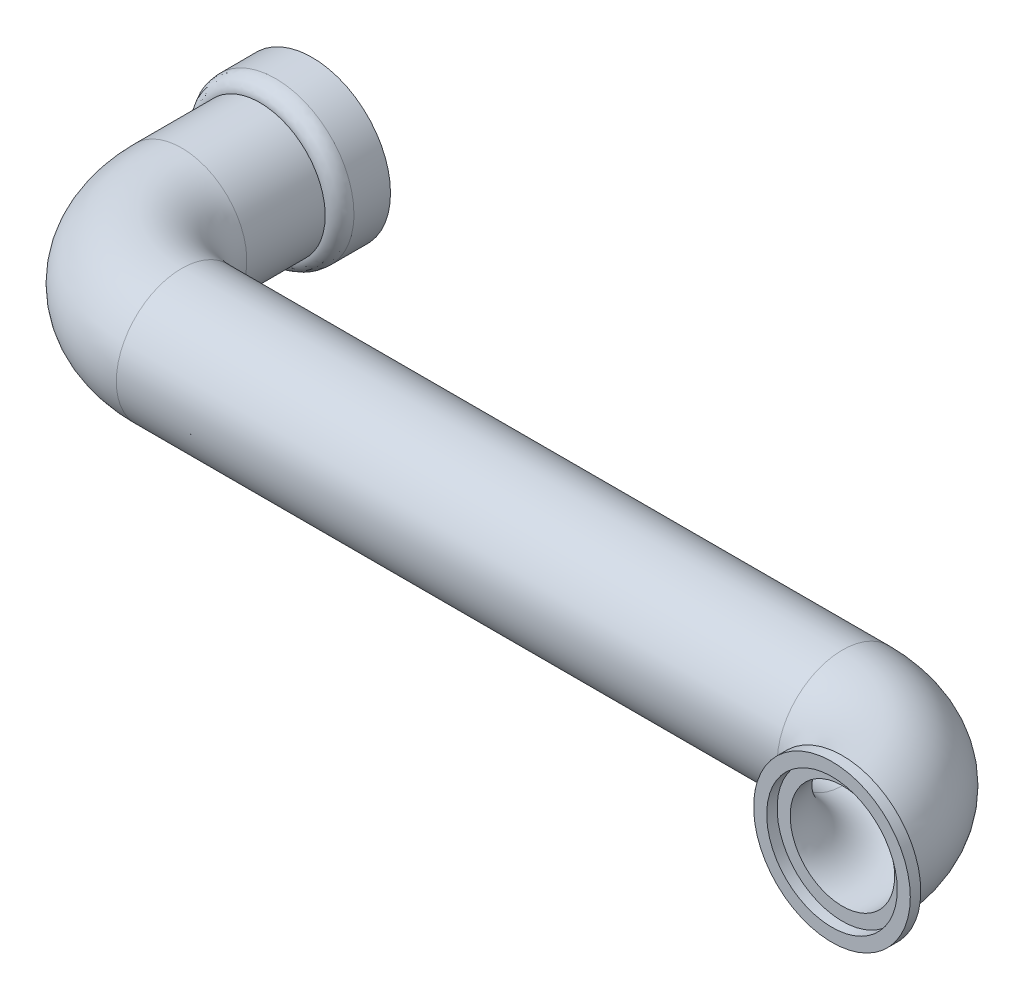
SolidWorks part; units mm, degrees
ref_plane "Alzado" through (0, 0, 0) normal (0, 0, 1) x (1, 0, 0)
ref_plane "Planta" through (0, 0, 0) normal (0, 1, 0) x (1, 0, 0)
ref_plane "Vista lateral" through (0, 0, 0) normal (1, 0, 0) x (0, 0, -1)
sketch "Croquis1" plane through (0, 0, 0) normal (0, 0, 1) x (1, 0, 0)
  circle A0 centre (0, 0) radius 12.5
  circle A1 centre (0, 0) radius 15
extrude "Saliente-Extruir1" add sketch "Croquis1" along normal blind 10
sketch "Croquis2" plane through (0, 0, 10) normal (0, 0, 1) x (1, 0, 0)
  circle A0 centre (0, 0) radius 12.5
  circle A1 centre (0, 0) radius 10
extrude "Saliente-Extruir2" add sketch "Croquis2" along normal blind 15 separate body
fillet "Redondeo3" radius 3 1 edges at (15, 0, 10) second distance 2.5 first distance on face at (15, 0, 10)
sketch "Croquis3" plane through (0, 0, 10) normal (0, 0, -1) x (-1, 0, 0)
  circle A0 centre (0, 0) radius 10
  circle A1 centre (0, 0) radius 12.5
extrude "Saliente-Extruir3" add sketch "Croquis3" along normal blind 1
sketch "Croquis5" plane through (0, 0, 0) normal (0, 1, 0) x (1, 0, 0)
  line L1 (-12.5, -25) -> (12.5, -25) construction
  line L3 (20, -45) -> (146.5317, -45)
  arc A0 (0, -25) -> (20, -45) centre (20, -25) ccw
  arc A1 (146.5317, -45) -> (166.5317, -65) centre (146.5317, -65) cw
sketch "Croquis6" plane through (0, 0, 25) normal (0, 0, 1) x (1, 0, 0)
  circle A0 centre (0, 0) radius 10
  circle A1 centre (0, 0) radius 12.5
sweep "Barrer1" add profiles "Croquis6" path "Croquis5"
sketch "Croquis7" plane through (0, 0, 65) normal (0, 0, 1) x (1, 0, 0)
  line L0 (166.5317, 0) -> (146.5317, 0) construction
  circle A0 centre (166.5317, 0) radius 12.5
  circle A1 centre (166.5317, 0) radius 15
  circle A2 centre (166.5317, 0) radius 10 construction
extrude "Saliente-Extruir4" add sketch "Croquis7" along normal blind 2 separate body
